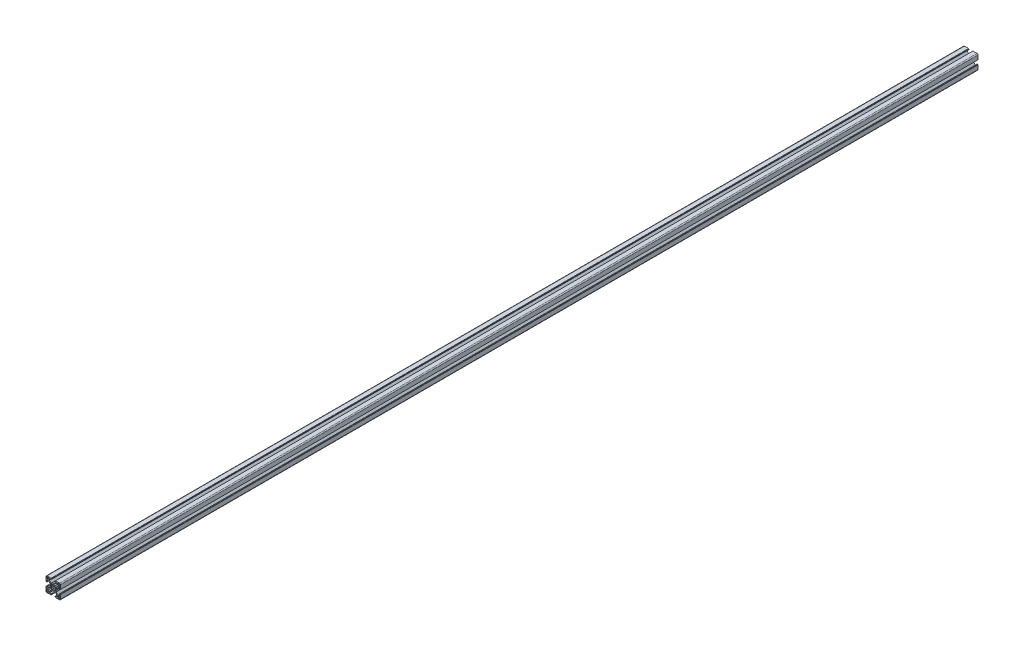
SolidWorks part; units mm, degrees
ref_plane "Front Plane" through (0, 0, 0) normal (0, 0, 1) x (1, 0, 0)
ref_plane "Top Plane" through (0, 0, 0) normal (0, 1, 0) x (1, 0, 0)
ref_plane "Right Plane" through (0, 0, 0) normal (1, 0, 0) x (0, 0, -1)
sketch "Sketch1" plane through (0, 0, 0) normal (0, 0, 1) x (1, 0, 0)
  line L0 (-15, 0) -> (15, 0) construction
  line L1 (0, -15) -> (0, 15) construction
  line L2 (-4.5, 15) -> (4.5, 15) construction
  line L3 (-4, -15) -> (4, -15) construction
  line L4 (-4.5, 15) -> (-4.5, 14.5)
  line L5 (-4.5, 14.5) -> (-4, 14.5)
  line L6 (-4, 14.5) -> (-4, 13.29)
  line L7 (-4.5, 12.79) -> (-7.7675, 12.79)
  line L8 (-8.2675, 12.29) -> (-8.2675, 10.2707)
  line L9 (-8.1211, 9.9171) -> (-4.3504, 6.1464)
  line L10 (-3.9968, 6) -> (0, 6)
  line L11 (0, 0) -> (-15, 15) construction
  line L12 (-4.5, 15) -> (-12.968, 15)
  line L14 (-12.705, 9.5135) -> (-10.5135, 9.5135)
  line L15 (-13.705, 10.5135) -> (-13.705, 12.705)
  line L16 (-12.705, 13.705) -> (-10.5135, 13.705)
  line L17 (-9.5135, 10.5135) -> (-9.5135, 12.705)
  line L18 (-13.705, 9.5135) -> (-9.5135, 13.705) construction
  line L19 (-13.705, 13.705) -> (-9.5135, 9.5135) construction
  line L20 (-3.1568, 4.5038) -> (-1.5303, 3.1477) construction
  line L21 (-4.5038, 3.1568) -> (-3.1477, 1.5303) construction
  line L22 (-6, 3.9968) -> (-6, 0)
  line L23 (-9.9171, 8.1211) -> (-6.1464, 4.3504)
  line L24 (-15, 4.5) -> (-15, 12.968)
  line L25 (-12.29, 8.2675) -> (-10.2707, 8.2675)
  line L26 (-12.79, 4.5) -> (-12.79, 7.7675)
  line L27 (-14.5, 4) -> (-13.29, 4)
  line L28 (-14.5, 4.5) -> (-14.5, 4)
  line L29 (-15, 4.5) -> (-14.5, 4.5)
  circle A0 centre (0, 0) radius 3.5
  arc A1 (-12.968, 15) -> (-15, 12.968) centre (-12.968, 12.968) ccw
  circle A2 centre (0, 0) radius 5.5 construction
  arc A3 (-10.5135, 9.5135) -> (-9.5135, 10.5135) centre (-10.5135, 10.5135) ccw
  arc A4 (-13.705, 12.705) -> (-12.705, 13.705) centre (-12.705, 12.705) cw
  arc A5 (-10.5135, 13.705) -> (-9.5135, 12.705) centre (-10.5135, 12.705) cw
  arc A6 (-12.705, 9.5135) -> (-13.705, 10.5135) centre (-12.705, 10.5135) cw
  arc A7 (-12.79, 4.5) -> (-13.29, 4) centre (-13.29, 4.5) cw
  arc A8 (-12.29, 8.2675) -> (-12.79, 7.7675) centre (-12.29, 7.7675) ccw
  arc A9 (-9.9171, 8.1211) -> (-10.2707, 8.2675) centre (-10.2707, 7.7675) ccw
  arc A10 (-6, 3.9968) -> (-6.1464, 4.3504) centre (-6.5, 3.9968) ccw
  arc A11 (-4.3504, 6.1464) -> (-3.9968, 6) centre (-3.9968, 6.5) ccw
  arc A12 (-4, 13.29) -> (-4.5, 12.79) centre (-4.5, 13.29) cw
  arc A13 (-7.7675, 12.79) -> (-8.2675, 12.29) centre (-7.7675, 12.29) ccw
  arc A14 (-8.2675, 10.2707) -> (-8.1211, 9.9171) centre (-7.7675, 10.2707) ccw
  point P4 (0, 0)
  point P8 (0, 0)
  point P13 (0, 15)
  point P15 (0, -15)
  point P16 (0, 6)
  point P23 (-11.6092, 11.6093)
  point P26 (0, 6)
  point P62 (-12.79, 4)
  point P65 (-12.79, 8.2675)
  point P68 (-10.0636, 8.2675)
  point P71 (-6, 4.2039)
  point P74 (-4.2039, 6)
  point P77 (-4, 12.79)
  point P80 (-8.2675, 12.79)
  point P83 (-8.2675, 10.0636)
  dimension "Center Hole Diameter" = 7
  dimension "D11" = 2.032
  dimension "D9" = 11
  dimension "D13" = 1
  dimension "D14" = 0.5
  dimension "Rail Height" = 30
  dimension "Rail Width" = 30
  dimension "T-Slot Width" = 8
  dimension "T-Slot Depth" = 9
  dimension "D1" = 9
  dimension "D2" = 45
  dimension "D3" = 8
  dimension "D4" = 2.21
  dimension "D5" = 16.535
  dimension "D7" = 2.54
  dimension "D6" = 1.295
  dimension "D8" = 1.246
  dimension "D10" = 10.36
  dimension "D12" = 1.905
sketch "Sketch2" plane through (0, 0, 0) normal (1, 0, 0) x (0, 0, -1)
  line L0 (-76.2, 0) -> (76.2, 0) construction
  line L2 (0, -15) -> (0, 15) construction
  line L3 (0, -15) -> (0, 15) construction
  line L4 (-76.2, -15) -> (-76.2, 15) construction
  line L5 (76.2, -15) -> (76.2, 15) construction
  point P0 (-38.7, 0)
  point P3 (0, 0)
  point P4 (38.7, 0)
  point P12 (-76.2, 0)
  point P14 (76.2, 0)
  dimension "Length" = 152.4
  dimension "D1" = 37.5
sketch "Sketch3" plane through (0, 0, 0) normal (0, 0, 1) x (1, 0, 0)
  line L0 (-4.5038, 3.1568) -> (-3.1477, 1.5303)
  line L1 (0, 3.5) -> (0, 5.5)
  line L2 (-5.5, 0) -> (-3.5, 0)
  line L7 (-6, 3.9968) -> (-6, 0) construction
  line L31 (-9.9171, 8.1211) -> (-6.1464, 4.3504) construction
  line L117 (-12.29, 8.2675) -> (-10.2707, 8.2675) construction
  line L118 (-12.79, 4.5) -> (-12.79, 7.7675) construction
  line L157 (-12.705, 9.5135) -> (-10.5135, 9.5135)
  line L158 (-9.5135, 10.5135) -> (-9.5135, 12.705)
  line L163 (-10.5135, 13.705) -> (-12.705, 13.705)
  line L164 (-13.705, 12.705) -> (-13.705, 10.5135)
  line L165 (-12.705, 9.5135) -> (-10.5135, 9.5135)
  line L166 (-9.5135, 10.5135) -> (-9.5135, 12.705)
  line L167 (-10.5135, 13.705) -> (-12.705, 13.705)
  line L168 (-13.705, 12.705) -> (-13.705, 10.5135)
  line L169 (-14.5, 4) -> (-13.29, 4) construction
  line L170 (-14.5, 4.5) -> (-14.5, 4) construction
  line L171 (-15, 4.5) -> (-14.5, 4.5) construction
  line L172 (-15, 4.5) -> (-15, 12.968) construction
  line L173 (-4.5, 15) -> (-12.968, 15) construction
  line L174 (-4.5, 15) -> (-4.5, 14.5) construction
  line L175 (-4.5, 14.5) -> (-4, 14.5) construction
  line L176 (-4, 14.5) -> (-4, 13.29) construction
  line L177 (-4.5, 12.79) -> (-7.7675, 12.79) construction
  line L178 (-8.2675, 12.29) -> (-8.2675, 10.2707) construction
  line L179 (-8.1211, 9.9171) -> (-4.3504, 6.1464) construction
  line L180 (-3.9968, 6) -> (0, 6) construction
  line L181 (-6, 3.9968) -> (-6, 0.866)
  line L182 (-9.9171, 8.1211) -> (-6.1464, 4.3504)
  line L183 (-12.29, 8.2675) -> (-10.2707, 8.2675)
  line L184 (-12.79, 4.5) -> (-12.79, 7.7675)
  line L185 (-14.5, 4) -> (-13.29, 4)
  line L186 (-14.5, 4.5) -> (-14.5, 4)
  line L187 (-15, 4.5) -> (-14.5, 4.5)
  line L188 (-15, 4.5) -> (-15, 12.968)
  line L189 (-4.5, 15) -> (-12.968, 15)
  line L190 (-4.5, 15) -> (-4.5, 14.5)
  line L191 (-4.5, 14.5) -> (-4, 14.5)
  line L192 (-4, 14.5) -> (-4, 13.29)
  line L193 (-4.5, 12.79) -> (-7.7675, 12.79)
  line L194 (-8.2675, 12.29) -> (-8.2675, 10.2707)
  line L195 (-8.1211, 9.9171) -> (-4.3504, 6.1464)
  line L196 (-3.9968, 6) -> (-0.866, 6)
  line L197 (-0.866, 6) -> (0, 5.5)
  line L198 (0, -15) -> (0, 15) construction
  line L199 (0, 0) -> (-15, 15) construction
  line L200 (0, 0) -> (-15, 15) construction
  line L201 (-3.1568, 4.5038) -> (-1.5303, 3.1477) construction
  line L202 (-3.1568, 4.5038) -> (-1.5303, 3.1477)
  line L203 (-6, 0.866) -> (-5.5, 0)
  line L204 (-15, 0) -> (15, 0) construction
  line L205 (-15, 0) -> (15, 0) construction
  line L206 (0, -15) -> (0, 15) construction
  arc A0 (-3.5, 0) -> (-3.1477, 1.5303) centre (0, 0) cw
  arc A10 (-6, 3.9968) -> (-6.1464, 4.3504) centre (-6.5, 3.9968) ccw construction
  circle A16 centre (0, 0) radius 3.5
  arc A18 (0, 3.5) -> (-1.5303, 3.1477) centre (0, 0) ccw
  arc A20 (-9.9171, 8.1211) -> (-10.2707, 8.2675) centre (-10.2707, 7.7675) ccw construction
  arc A22 (-12.29, 8.2675) -> (-12.79, 7.7675) centre (-12.29, 7.7675) ccw construction
  arc A28 (-13.29, 4) -> (-12.79, 4.5) centre (-13.29, 4.5) ccw construction
  arc A29 (-10.5135, 9.5135) -> (-9.5135, 10.5135) centre (-10.5135, 10.5135) ccw
  arc A30 (-9.5135, 12.705) -> (-10.5135, 13.705) centre (-10.5135, 12.705) ccw
  arc A31 (-12.705, 13.705) -> (-13.705, 12.705) centre (-12.705, 12.705) ccw
  arc A32 (-13.705, 10.5135) -> (-12.705, 9.5135) centre (-12.705, 10.5135) ccw
  arc A33 (-10.5135, 9.5135) -> (-9.5135, 10.5135) centre (-10.5135, 10.5135) ccw
  arc A34 (-9.5135, 12.705) -> (-10.5135, 13.705) centre (-10.5135, 12.705) ccw
  arc A35 (-12.705, 13.705) -> (-13.705, 12.705) centre (-12.705, 12.705) ccw
  arc A36 (-13.705, 10.5135) -> (-12.705, 9.5135) centre (-12.705, 10.5135) ccw
  arc A37 (-12.968, 15) -> (-15, 12.968) centre (-12.968, 12.968) ccw construction
  arc A38 (-4.5, 12.79) -> (-4, 13.29) centre (-4.5, 13.29) ccw construction
  arc A39 (-7.7675, 12.79) -> (-8.2675, 12.29) centre (-7.7675, 12.29) ccw construction
  arc A40 (-8.2675, 10.2707) -> (-8.1211, 9.9171) centre (-7.7675, 10.2707) ccw construction
  arc A41 (-4.3504, 6.1464) -> (-3.9968, 6) centre (-3.9968, 6.5) ccw construction
  arc A42 (-6, 3.9968) -> (-6.1464, 4.3504) centre (-6.5, 3.9968) ccw
  arc A43 (-9.9171, 8.1211) -> (-10.2707, 8.2675) centre (-10.2707, 7.7675) ccw
  arc A44 (-12.29, 8.2675) -> (-12.79, 7.7675) centre (-12.29, 7.7675) ccw
  arc A45 (-13.29, 4) -> (-12.79, 4.5) centre (-13.29, 4.5) ccw
  arc A46 (-12.968, 15) -> (-15, 12.968) centre (-12.968, 12.968) ccw
  arc A47 (-4.5, 12.79) -> (-4, 13.29) centre (-4.5, 13.29) ccw
  arc A48 (-7.7675, 12.79) -> (-8.2675, 12.29) centre (-7.7675, 12.29) ccw
  arc A49 (-8.2675, 10.2707) -> (-8.1211, 9.9171) centre (-7.7675, 10.2707) ccw
  arc A50 (-4.3504, 6.1464) -> (-3.9968, 6) centre (-3.9968, 6.5) ccw
  circle A51 centre (0, 0) radius 5.5 construction
  arc A52 (-3.1568, 4.5038) -> (-4.5038, 3.1568) centre (0, 0) ccw
  dimension "D3" = 60
  dimension "D4" = 60
  dimension "D1" = 0
  dimension "D2" = 0
extrude "Boss-Extrude1" add sketch "Sketch3" along normal mid plane 1900
pattern_circular "CirPattern1" count 4 over 360 about axis through (0, 0, 76.2) along (0, 0, -1) of "Boss-Extrude1"
ref_plane "Contact Plane1" through (15, 0, 0) normal (1, 0, 0) x (0, 0, -1)
ref_plane "Contact Plane2" through (0, -15, 0) normal (0, 1, 0) x (1, 0, 0)
ref_plane "Contact Plane3" through (-15, 0, 0) normal (1, 0, 0) x (0, 0, -1)
ref_plane "Contact Plane4" through (0, 15, 0) normal (0, 1, 0) x (1, 0, 0)
equation "\"D1@Sketch2\" = \"Rail Height@Sketch1\" * 1.25"
equation "\"D1@Sketch1\"=\"T-Slot Width@Sketch1\"+1mm"
equation "\"D3@Sketch1\"=\"T-Slot Width@Sketch1\""
equation "\"D1@Boss-Extrude1\"=\"length\""
equation "\"length\"= 1900"
